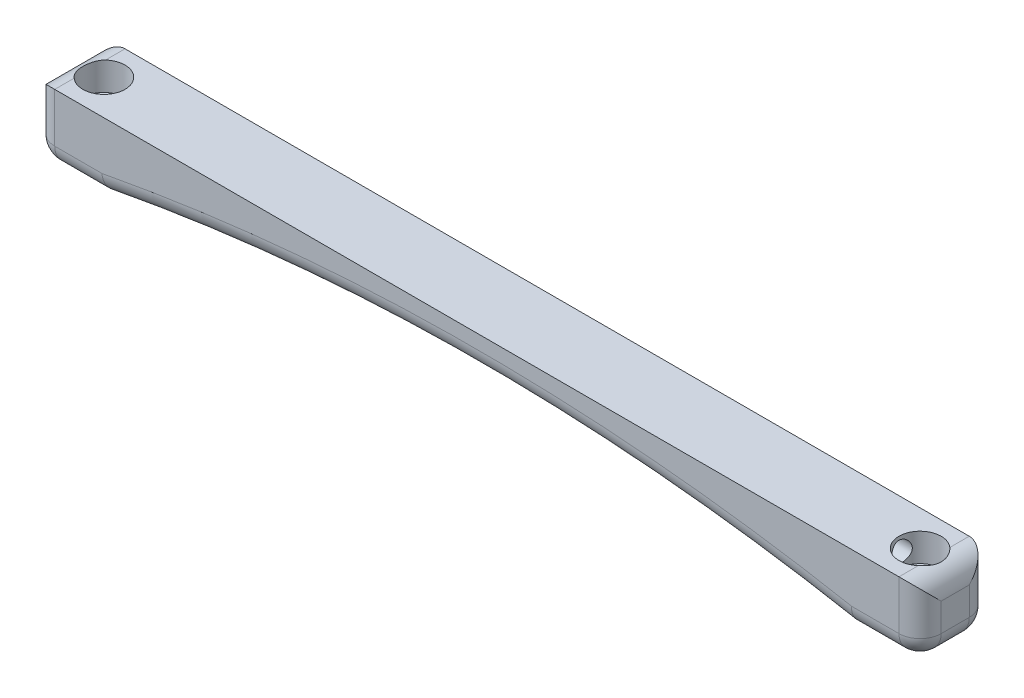
SolidWorks part; units mm, degrees
ref_plane "Plano frontal" through (0, 0, 0) normal (0, 0, 1) x (1, 0, 0)
ref_plane "Plano superior" through (0, 0, 0) normal (0, 1, 0) x (1, 0, 0)
ref_plane "Plano direito" through (0, 0, 0) normal (1, 0, 0) x (0, 0, -1)
sketch "Esboço1" plane through (0, 0, 0) normal (0, 0, 1) x (1, 0, 0)
  line L1 (-63.05, -5) -> (63.05, -5)
  line L2 (-63.05, -5) -> (-63.05, 5)
  line L3 (-63.05, 5) -> (63.05, 5)
  line L4 (63.05, -5) -> (63.05, 5)
  line L5 (-63.05, -5) -> (63.05, 5) construction
  line L6 (-63.05, 5) -> (63.05, -5) construction
  point P0 (0, 0)
  dimension "D1" = 126.1
  dimension "D2" = 10
extrude "Ressalto-extrusão1" add sketch "Esboço1" along normal blind 10
sketch "Esboço2" plane through (0, 0, 10) normal (0, 0, 1) x (1, 0, 0)
  line L0 (-63.05, -5) -> (63.05, -5) construction
  line L1 (-63.05, -5) -> (-53.05, -5) construction
  line L2 (63.05, -5) -> (53.05, -5) construction
  arc A0 (-53.05, -5) -> (53.05, -5) centre (0, -283.9302) cw
  dimension "D1" = 10
  dimension "D2" = 10
extrude "Corte-extrusão1" cut sketch "Esboço2" against normal through all flip side to cut
sketch "Esboço3" plane through (0, -5, 0) normal (0, 1, 0) x (1, 0, 0)
  line L0 (-63.05, -10) -> (-63.05, 0) construction
  line L3 (-63.05, -5) -> (-58.05, -5) construction
  line L5 (-56.354, -7.9468) -> (-54.65, -5.0046)
  line L6 (-54.65, -5.0046) -> (-56.346, -2.0578)
  line L7 (-56.346, -2.0578) -> (-59.746, -2.0532)
  line L8 (-59.746, -2.0532) -> (-61.45, -4.9954)
  line L9 (-61.45, -4.9954) -> (-59.754, -7.9422)
  line L10 (-59.754, -7.9422) -> (-56.354, -7.9468)
  circle A0 centre (-58.05, -5) radius 2.9445 construction
  dimension "D1" = 5
  dimension "D2" = 3.4
extrude "Corte-extrusão3" cut sketch "Esboço3" along normal blind 3
sketch "Esboço4" plane through (0, 5, 0) normal (0, 1, 0) x (1, 0, 0)
  line L0 (-63.05, 0) -> (-63.05, -10) construction
  line L1 (-63.05, -5) -> (-58.05, -5) construction
  circle A0 centre (-58.05, -5) radius 3
  dimension "D2" = 6
  dimension "D1" = 5
extrude "Corte-extrusão4" cut sketch "Esboço4" against normal blind 4
sketch "Esboço5" plane through (0, 1, 0) normal (0, 1, 0) x (1, 0, 0)
  circle A0 centre (-58.05, -5) radius 1.25
  dimension "D1" = 2.5
extrude "Corte-extrusão5" cut sketch "Esboço5" against normal through all
mirror "Espelhar2" about plane through (0, 0, 0) normal (1, 0, 0) of "Corte-extrusão5", "Corte-extrusão4", "Corte-extrusão3"
sketch "Esboço6" plane through (0, 0, 0) normal (-1, 0, 0) x (0, 0, 1)
  line L0 (5, 5) -> (5, 3) construction
  line L1 (10, 5) -> (0, 5) construction
  circle A0 centre (5, 3) radius 1.5
  dimension "D2" = 3
  dimension "D1" = 2
extrude "Corte-extrusão9" cut sketch "Esboço6" against normal up to next and the other way up to next
fillet "Filete1" radius 3 6 edges at (-63.05, 5, 5) (-63.05, 0, 10) (-63.05, 0, 0) (63.05, 0, 0) (63.05, 0, 10) (63.05, 5, 5)
fillet "Filete2" radius 3 6 edges at (56.55, -5, 0) (56.55, -5, 10) (-56.55, -5, 10) (-56.55, -5, 0) (0, 0, 0) (0, 0, 10)
